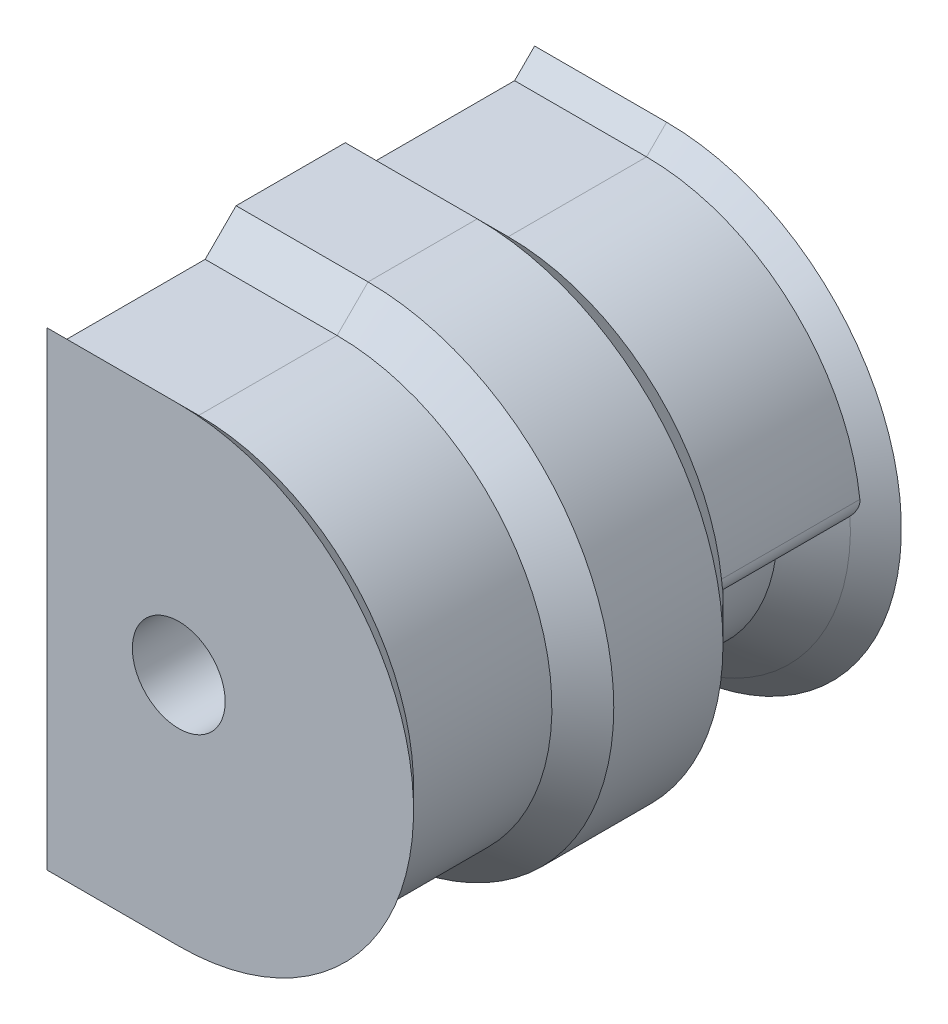
SolidWorks part; units mm, degrees
ref_plane "Front Plane" through (0, 0, 0) normal (0, 0, 1) x (1, 0, 0)
ref_plane "Top Plane" through (0, 0, 0) normal (0, 1, 0) x (1, 0, 0)
ref_plane "Right Plane" through (0, 0, 0) normal (1, 0, 0) x (0, 0, -1)
sketch "Sketch1" plane through (0, 0, 0) normal (0, 0, 1) x (1, 0, 0)
  line L0 (-7.25, -13.5) -> (-7.25, 13.5)
  line L1 (0, 13.5) -> (-7.25, 13.5)
  line L2 (0, -13.5) -> (-7.25, -13.5)
  line L3 (0, 4.075) -> (-7.25, 4.075)
  line L4 (0, -4.075) -> (-7.25, -4.075)
  circle A0 centre (0, 0) radius 2.55
  circle A1 centre (0, 0) radius 14 construction
  arc A2 (0, -13.5) -> (0, 13.5) centre (0, 0) ccw
  circle A3 centre (0, 0) radius 13.5 construction
  arc A4 (0, -4.075) -> (0, 4.075) centre (0, 0) ccw
  point P6 (-7.25, 0)
  dimension "D1" = 5.1
  dimension "D3" = 28
  dimension "D5" = 8.15
  dimension "D2" = 7.25
  dimension "D4" = 0.5
extrude "Boss-Extrude3" add sketch "Sketch1" along normal mid plane 26.8 contours A4 L4 L0 L2 A2 L1 L3 | L4 A4 L3 L0 A0 region at (-6.9095, -8.7875, 0) region at (-2.6115, 0, 0)
extrude "Cut-Extrude1" cut sketch "Sketch1<4>" against normal mid plane 10.05 contours L4 A4 L3 L0 A0 region at (-2.6115, 0, 0)
sketch "Sketch1<4>" plane through (0, 0, 0) normal (0, 0, 1) x (1, 0, 0) same geometry as "Sketch1"
ref_plane "Plane2" through (0, 0, 8.5) normal (0, 0, 1) x (1, 0, 0)
sketch "Sketch2" plane through (0, 0, 8.5) normal (0, 0, 1) x (1, 0, 0)
  line L0 (-7.25, -13.5) -> (-7.25, 13.5) construction
  line L1 (2.3036, -9.2165) -> (2.5618, -11.5186)
  line L2 (1.8127, -9.3255) -> (2.0697, -11.6171)
  line L3 (0, 11.8) -> (-7.25, 11.8)
  line L4 (-1.1084, 9.9887) -> (1.3272, -11.7251) construction
  line L6 (0, -11.8) -> (-7.25, -11.8)
  line L8 (-1.1084, 9.9887) -> (1.4148, -12.5065) construction
  line L13 (0, 13.5) -> (-7.25, 13.5)
  line L14 (-7.25, 13.5) -> (-7.25, -13.5)
  line L15 (-7.25, -13.5) -> (0, -13.5)
  line L16 (0, 13.5) -> (-7.25, 13.5)
  line L18 (-7.25, 13.5) -> (-7.25, 9.5)
  line L19 (-7.25, -13.5) -> (0, -13.5)
  line L20 (0, -9.5) -> (-7.25, -9.5)
  line L21 (0, 9.5) -> (-7.25, 9.5)
  line L22 (-7.25, -9.5) -> (-7.25, -13.5)
  line L23 (-0.3631, 10.0723) -> (2.1601, -12.4229) construction
  line L24 (2.3096, -9.2697) -> (2.5666, -11.5613) construction
  arc A0 (0, -11.8) -> (0, 11.8) centre (0, 0) ccw
  arc A1 (0, -13.5) -> (0, 13.5) centre (0, 0) ccw
  arc A2 (0, -13.5) -> (0, 13.5) centre (0, 0) ccw
  arc A5 (0, -9.5) -> (1.0708, -9.4395) centre (0, 0) ccw
  arc A6 (1.0708, -9.4395) -> (0, 9.5) centre (0, 0) ccw
  arc A7 (0, -9.5) -> (0, 9.5) centre (0, 0) ccw construction
  dimension "D6" = 1.7
  dimension "D1" = 6.4
  dimension "D5" = 4
  dimension "D2" = 0.5
  dimension "D3" = 0.75
  dimension "D4" = 0
extrude "Cut-Extrude2" cut sketch "Sketch2" against normal mid plane 7 contours L4 | A5 L20 L22 L19 A2 | L19 A2 L16 L18 L3 A0 L6 L22 | A6 L2 A0 L1 region at (2.1874, -10.4213, 8.5) region at (12.0679, 1.3258, 8.5) region at (-2.6492, -10.6427, 8.5)
ref_plane "Plane3" through (0, 0, -8.5) normal (0, 0, 1) x (1, 0, 0)
sketch "Sketch3" plane through (0, 0, -8.5) normal (0, 0, 1) x (1, 0, 0)
  line L0 (0, 0) -> (7.5976, 0) construction
  line L2 (9.4703, 0.75) -> (11.7761, 0.75)
  line L3 (0, 9.5) -> (-7.25, 9.5)
  line L4 (-7.25, -13.5) -> (-7.25, 13.5) construction
  line L5 (0, -9.5) -> (-7.25, -9.5)
  line L6 (-7.25, -9.5) -> (-7.25, -13.5)
  line L7 (0, 11.8) -> (-7.25, 11.8)
  line L8 (0, 0.75) -> (7.5976, 0.75) construction
  line L9 (0, 13.5) -> (-7.25, 13.5)
  line L10 (-7.25, -13.5) -> (0, -13.5)
  line L11 (-7.25, 13.5) -> (-7.25, -13.5)
  line L12 (0, 13.5) -> (-7.25, 13.5)
  line L13 (-7.25, -13.5) -> (0, -13.5)
  line L14 (-7.25, 13.5) -> (-7.25, 9.5)
  line L15 (9.4967, 0.25) -> (11.7974, 0.25)
  line L16 (0, -11.8) -> (-7.25, -11.8)
  line L17 (9.4703, 0.25) -> (11.7761, 0.25) construction
  arc A0 (0, -11.8) -> (0, 11.8) centre (0, 0) ccw
  arc A1 (9.4703, 0.75) -> (0, 9.5) centre (0, 0) ccw
  arc A2 (0, -9.5) -> (0, 9.5) centre (0, 0) ccw
  arc A3 (0, -9.5) -> (9.4703, 0.75) centre (0, 0) ccw
  arc A5 (0, -13.5) -> (0, 13.5) centre (0, 0) ccw
  arc A6 (0, -13.5) -> (0, 13.5) centre (0, 0) ccw
  dimension "D5" = 0.5
  dimension "D2" = 1.7
  dimension "D1" = 4
  dimension "D3" = 0.75
  dimension "D4" = 0
extrude "Cut-Extrude3" cut sketch "Sketch3" against normal mid plane 7 contours A3 L5 L6 L16 A0 L2 | L13 A6 L12 L14 L7 A0 L16 L6 region at (8.3074, 8.8533, -8.5) region at (10.647, 0.0246, -8.5)
fillet "Fillet1" radius 1 2 edges at (2.5618, -11.5186, 8.5) (11.7974, 0.25, -8.5)
sketch "Sketch4" plane through (-7.25, 0, 0) normal (-1, 0, 0) x (0, 0, 1)
  line L0 (0, -11.4125) -> (0, 11.4125) construction
  circle A1 centre (-9.5, 8) radius 1.75
  circle A2 centre (9.5, 8) radius 1.75
  dimension "D1" = 9.5
  dimension "D2" = 8
extrude "Cut-Extrude4" cut sketch "Sketch4" against normal blind 7
chamfer "Chamfer1" distance 2 angle 45 12 edges at (-3.625, -13.5, -12) (13.5, 0, -12) (13.5, 0, -5) (-3.625, -13.5, -5) (13.5, 0, 5) (-3.625, -13.5, 5) (13.5, 0, 12) (-3.625, -13.5, 12) (-3.625, 13.5, 5) (-3.625, 13.5, 12) (-3.625, 13.5, -12) (-3.625, 13.5, -5)
fillet "Fillet2" radius 3.15 2 edges at (-7.25, 4.075, 0) (-7.25, -4.075, 0)
chamfer "Chamfer2" distance 2 angle 45 8 edges at (1.1605, -9.4289, 12) (-3.625, -9.5, 12) (1.1605, -9.4289, 5) (-3.625, -9.5, 5) (-3.625, -9.5, -12) (6.8053, -6.6285, -12) (-3.625, -9.5, -5) (6.8053, -6.6285, -5)
